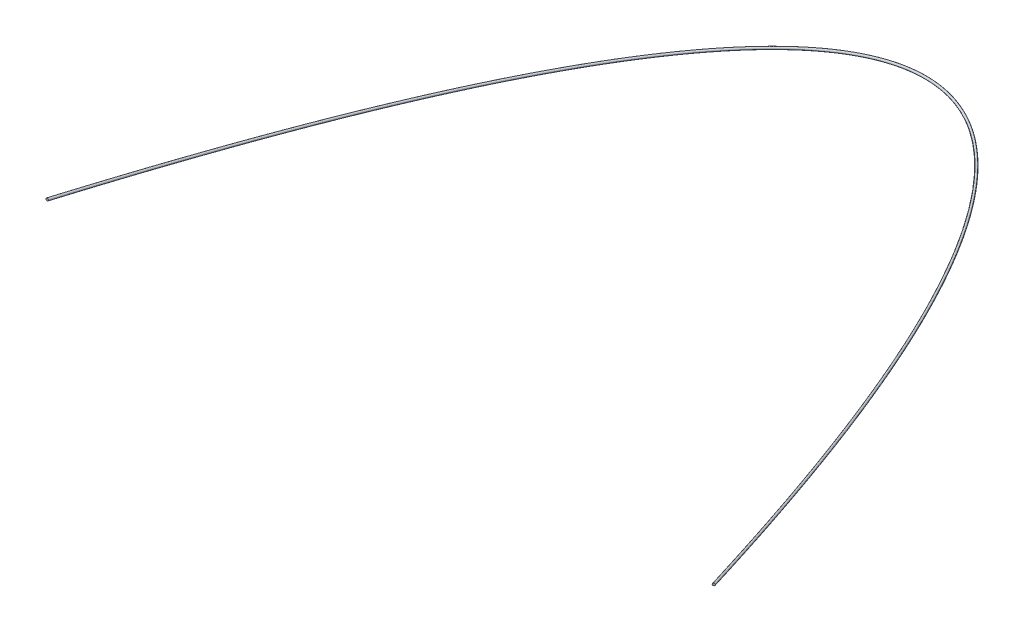
SolidWorks part; units mm, degrees
material "Copper"
ref_plane "Front Plane" through (0, 0, 0) normal (0, 0, 1) x (1, 0, 0)
ref_plane "Top Plane" through (0, 0, 0) normal (0, 1, 0) x (1, 0, 0)
ref_plane "Right Plane" through (0, 0, 0) normal (1, 0, 0) x (0, 0, -1)
sketch "Sketch1" plane through (0, 0, 0) normal (0, 1, 0) x (1, 0, 0)
  line L0 (0, 0) -> (125, 408.6503) construction
  line L1 (125, 408.6503) -> (250, 0) construction
  line L2 (0, 0) -> (250, 0) construction
  spline S0 degree 2 poles (0, 0) (125, 408.6503) (250, 0) knots 0 0 0 1 1 1
  point P3 (125, 0)
  dimension "D1" = 500
  dimension "D2" = 250
sketch "Sketch2" plane through (0, 0, 0) normal (0, 0, 1) x (1, 0, 0)
  circle A0 centre (0, 0) radius 0.35
  dimension "D1" = 0.7
sketch "Sketch3" plane through (0, 0, 0) normal (0, 0, 1) x (1, 0, 0)
  circle A0 centre (0, 0) radius 0.45
  circle A1 centre (0, 0) radius 0.35
  circle A2 centre (0, 0) radius 0.35 construction
  dimension "D2" = 0.9
sweep "Sweep1" add profiles "Sketch2" path "Sketch1"
sweep "Sweep2" add profiles "Sketch3" path "Sketch1<2>"
sketch "Sketch1<2>" plane through (0, 0, 0) normal (0, 1, 0) x (1, 0, 0) same geometry as "Sketch1"
